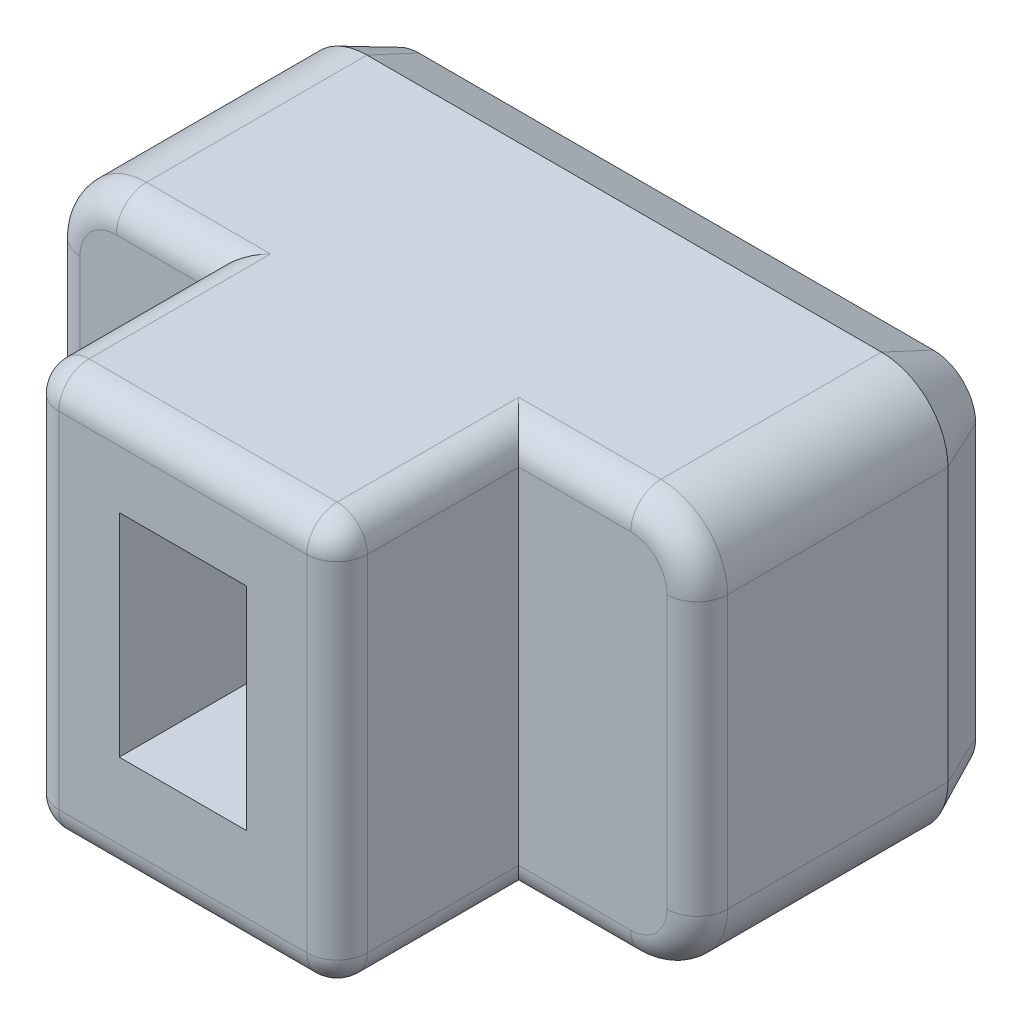
SolidWorks part; units mm, degrees
ref_plane "Plan de face" through (0, 0, 0) normal (0, 0, 1) x (1, 0, 0)
ref_plane "Plan de dessus" through (0, 0, 0) normal (0, 1, 0) x (1, 0, 0)
ref_plane "Plan de droite" through (0, 0, 0) normal (1, 0, 0) x (0, 0, -1)
sketch "Esquisse2" plane through (0, 0, 0) normal (0, 0, 1) x (1, 0, 0)
  line L1 (1.1, 0) -> (9.6, 0)
  line L2 (0, 1.1) -> (0, 5.6)
  line L3 (1.1, 6.7) -> (9.6, 6.7)
  line L4 (10.7, 1.1) -> (10.7, 5.6)
  arc A0 (9.6, 6.7) -> (10.7, 5.6) centre (9.6, 5.6) cw
  arc A1 (9.6, 0) -> (10.7, 1.1) centre (9.6, 1.1) ccw
  arc A2 (1.1, 0) -> (0, 1.1) centre (1.1, 1.1) cw
  arc A3 (0, 5.6) -> (1.1, 6.7) centre (1.1, 5.6) cw
  point P7 (10.7, 6.7)
  point P12 (0, 0)
  point P15 (0, 6.7)
  dimension "D3" = 1.1
  dimension "D1" = 10.7
  dimension "D2" = 6.7
extrude "Boss.-Extru.1" add sketch "Esquisse2" along normal blind 8
sketch "Esquisse3" plane through (0, 0, 8) normal (0, 0, 1) x (1, 0, 0)
  line L0 (0, 5.6) -> (0, 1.1) construction
  line L1 (4.15, 5.25) -> (6.25, 5.25)
  line L2 (4.15, 5.25) -> (4.15, 1.75)
  line L3 (4.15, 1.75) -> (6.25, 1.75)
  line L4 (6.25, 5.25) -> (6.25, 1.75)
  line L5 (10.7, 1.1) -> (10.7, 5.6) construction
  line L6 (9.6, 6.7) -> (1.1, 6.7) construction
  line L7 (1.1, 0) -> (9.6, 0) construction
  dimension "D1" = 2.1
  dimension "D2" = 3.5
  dimension "D3" = 4.15
  dimension "D4" = 4.45
  dimension "D5" = 1.45
  dimension "D6" = 1.75
extrude "Enlèv. mat.-Extru.1" cut sketch "Esquisse3" against normal blind 3
sketch "Esquisse4" plane through (0, 0, 8) normal (0, 0, 1) x (1, 0, 0)
  line L0 (2.65, 6.7) -> (2.65, 0)
  line L1 (9.6, 6.7) -> (1.1, 6.7) construction
  line L2 (1.1, 0) -> (9.6, 0) construction
  line L3 (2.65, 0) -> (7.75, 0)
  line L4 (7.75, 0) -> (7.75, 6.7)
  line L5 (7.75, 6.7) -> (2.65, 6.7)
  line L6 (4.15, 5.25) -> (4.15, 1.75) construction
  line L7 (6.25, 1.75) -> (6.25, 5.25) construction
  dimension "D1" = 1.5
  dimension "D2" = 1.5
extrude "Enlèv. mat.-Extru.2" cut sketch "Esquisse4" against normal blind 3 flip side to cut
fillet "Congé1" radius 0.5 18 edges at (8.675, 0, 5) (10.3778, 0.3222, 5) (10.7, 3.35, 5) (10.3778, 6.3778, 5) (1.875, 6.7, 5) (0.3222, 6.3778, 5) (1.875, 0, 5) (0.3222, 0.3222, 5) (7.75, 6.7, 6.5) (2.65, 6.7, 6.5) (7.75, 0, 6.5) (2.65, 0, 6.5) (2.65, 3.35, 8) (5.2, 6.7, 8) (7.75, 3.35, 8) (5.2, 0, 8) (8.675, 6.7, 5) (0, 3.35, 5)
chamfer "Chanfrein1" distance 0.4 angle 65 8 edges at (5.35, 0, 0) (10.3778, 0.3222, 0) (0.3222, 0.3222, 0) (10.7, 3.35, 0) (0, 3.35, 0) (10.3778, 6.3778, 0) (0.3222, 6.3778, 0) (5.35, 6.7, 0) first distance on face at (5.35, 3.35, 0)
ref_plane "Plan1" through (0, 0, 0.2) normal (0, 0, 1) x (1, 0, 0)
sketch "Esquisse5" plane through (0, 0, 0.2) normal (0, 0, 1) x (1, 0, 0)
  line L0 (-0.9378, 5.3566) -> (11.6517, 5.3566) construction
  text T0 "ALT" font "Century Gothic" height 4
extrude "Enlèv. mat.-Extru.3" cut sketch "Esquisse5" against normal blind 0.3
extrude "Boss.-Extru.2" add sketch "Esquisse5<3>" against normal blind 0.2 from offset 0.2 offset against normal yes
sketch "Esquisse5<3>" plane through (0, 0, 0.2) normal (0, 0, 1) x (1, 0, 0) same geometry as "Esquisse5"
